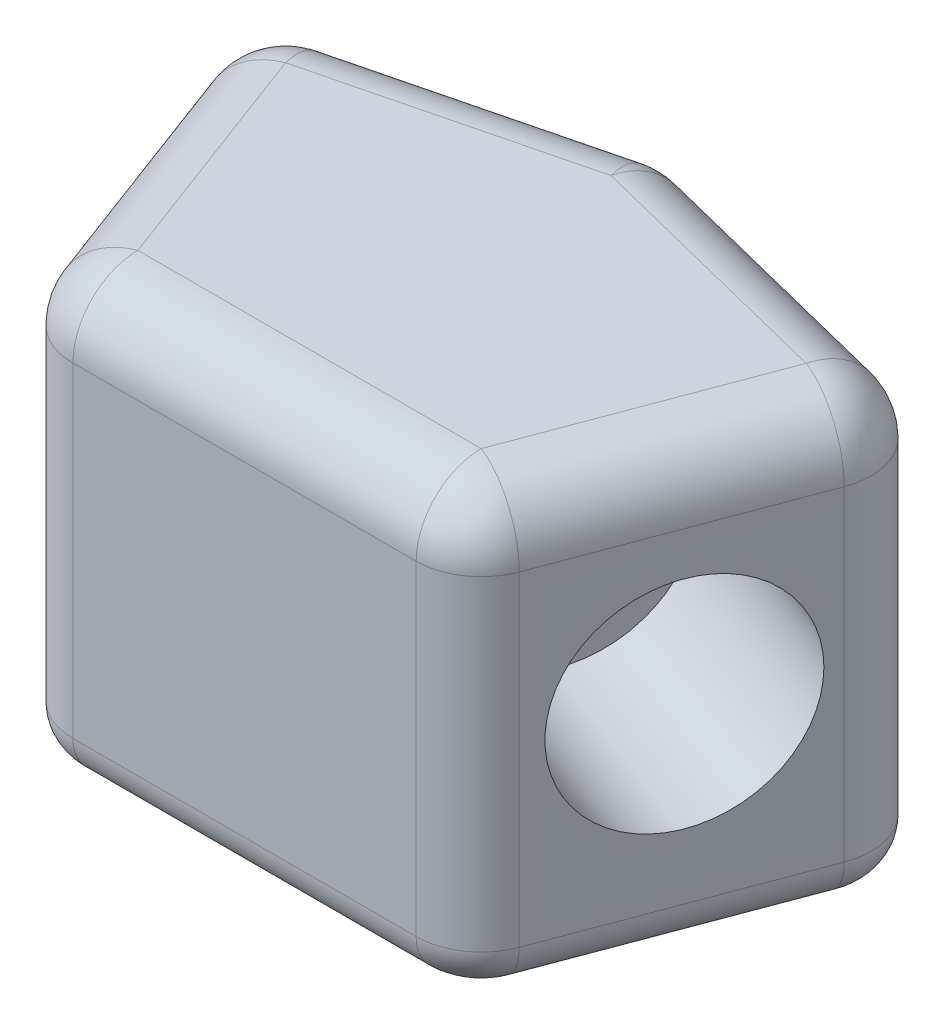
SolidWorks part; units mm, degrees
ref_plane "Front Plane" through (0, 0, 0) normal (0, 0, 1) x (1, 0, 0)
ref_plane "Top Plane" through (0, 0, 0) normal (0, 1, 0) x (1, 0, 0)
ref_plane "Right Plane" through (0, 0, 0) normal (1, 0, 0) x (0, 0, -1)
sketch "Sketch1" plane through (0, 0, 0) normal (0, 1, 0) x (1, 0, 0)
  line L0 (-5, 0) -> (5, 0)
  line L1 (5, 0) -> (8, 8)
  line L2 (8, 8) -> (0, 10)
  line L3 (0, 10) -> (-8, 8)
  line L4 (-8, 8) -> (-5, 0)
  dimension "D1" = 10
  dimension "D2" = 16
  dimension "D3" = 10
  dimension "D4" = 3
  dimension "D5" = 8
extrude "Boss-Extrude1" add sketch "Sketch1" along normal blind 10
sketch "Sketch2" plane through (4.3836, 0, 1.6438) normal (0.9363, 0, 0.3511) x (0.3511, 0, -0.9363)
  line L0 (1.7556, 10) -> (1.7556, 0) construction
  line L1 (1.7556, 10) -> (10.2996, 10) construction
  circle A0 centre (5.7556, 5) radius 2.5
  dimension "D1" = 5
  dimension "D2" = 4
  dimension "D3" = 5
extrude "Cut-Extrude1" cut sketch "Sketch2" against normal blind 5
sketch "Sketch3" plane through (-4.3836, 0, 1.6438) normal (-0.9363, 0, 0.3511) x (0.3511, 0, 0.9363)
  line L0 (-1.7556, 10) -> (-1.7556, 0) construction
  line L2 (-10.2996, 10) -> (-1.7556, 10) construction
  circle A0 centre (-5.7556, 5) radius 2.5
  dimension "D1" = 5
  dimension "D2" = 4
  dimension "D3" = 5
extrude "Cut-Extrude2" cut sketch "Sketch3" against normal blind 5 contours A0
sketch "Sketch4" plane through (0, 0, 0) normal (0, -1, 0) x (1, 0, 0)
  line L0 (-5, 0) -> (5, 0) construction
  circle A0 centre (0, -5) radius 1.5
  dimension "D1" = 3
  dimension "D2" = 5
extrude "Cut-Extrude3" cut sketch "Sketch4" against normal blind 1
fillet "Fillet1" radius 1.5 5 edges at (0, 5, -10) (-8, 5, -8) (-5, 5, 0) (5, 5, 0) (8, 5, -8)
fillet "Fillet2" radius 1.5 10 edges at (7.3332, 10, -7.6499) (6.3873, 10, -3.6996) (4.8149, 10, -0.2671) (0, 10, 0) (-4.8149, 10, -0.2671) (-6.3873, 10, -3.6996) (-7.3332, 10, -7.6499) (-3.3664, 10, -9.1584) (0, 10, -9.9538) (3.3664, 10, -9.1584)
fillet "Fillet3" radius 1 11 edges at (-7.3332, 0, -7.6499) (-6.3873, 0, -3.6996) (-4.8149, 0, -0.2671) (0, 0, 0) (4.8149, 0, -0.2671) (6.3873, 0, -3.6996) (7.3332, 0, -7.6499) (3.3664, 0, -9.1584) (0, 0, -9.9538) (-3.3664, 0, -9.1584) (0, 0, -6.5)
